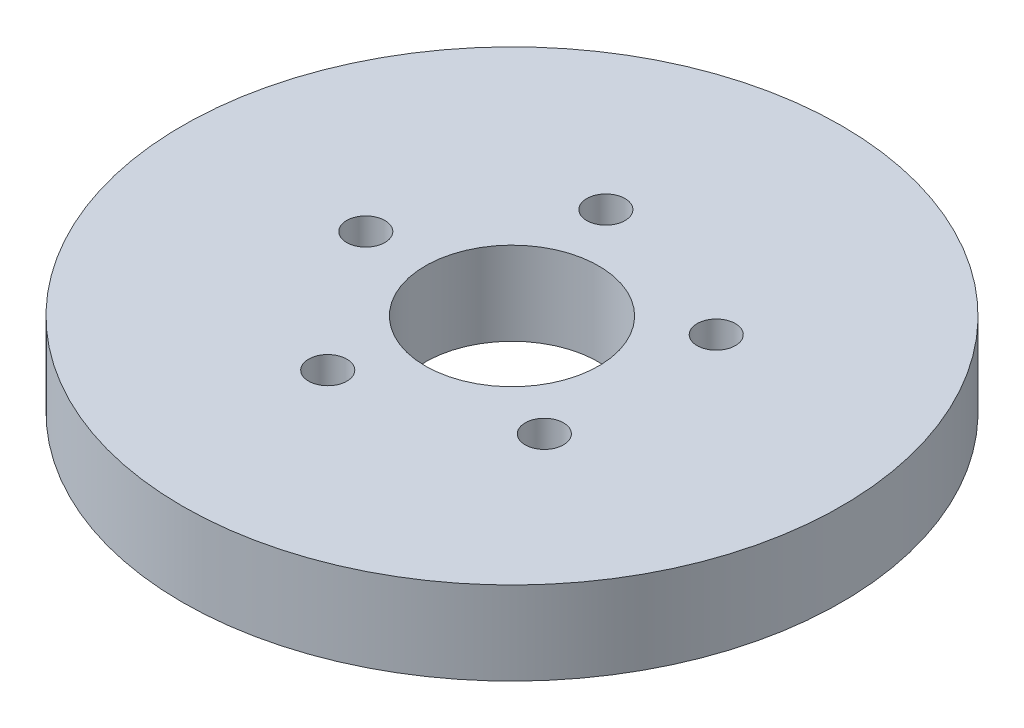
SolidWorks part; units mm, degrees
ref_plane "Front Plane" through (0, 0, 0) normal (0, 0, 1) x (1, 0, 0)
ref_plane "Top Plane" through (0, 0, 0) normal (0, 1, 0) x (1, 0, 0)
ref_plane "Right Plane" through (0, 0, 0) normal (1, 0, 0) x (0, 0, -1)
sketch "Sketch1" plane through (0, 0, 0) normal (0, 1, 0) x (1, 0, 0)
  circle A0 centre (0, 0) radius 95
  dimension "FLANGE_OD" = 190
extrude "Boss-Extrude1" add sketch "Sketch1" along normal blind 24
sketch "Sketch2" plane through (0, 0, 0) normal (0, 1, 0) x (1, 0, 0)
  circle A0 centre (0, 0) radius 25
  dimension "BORE_D" = 50
extrude "Cut-Extrude1" cut sketch "Sketch2" along normal through all
sketch "Sketch3" plane through (0, 24, 0) normal (0, 1, 0) x (1, 0, 0)
  circle A0 centre (0, 0) radius 42.1494 construction
  circle A1 centre (-42.1494, 0) radius 5.5161
  dimension "BOLT_D" = 11.0321
  dimension "BOLT_PCD" = 84.2989
extrude "Cut-Extrude2" cut sketch "Sketch3" against normal blind 18.435
pattern_circular "CirPattern1" count 5 over 360 about axis through (0, 0, 0) along (0, 1, 0) of "Cut-Extrude2"
